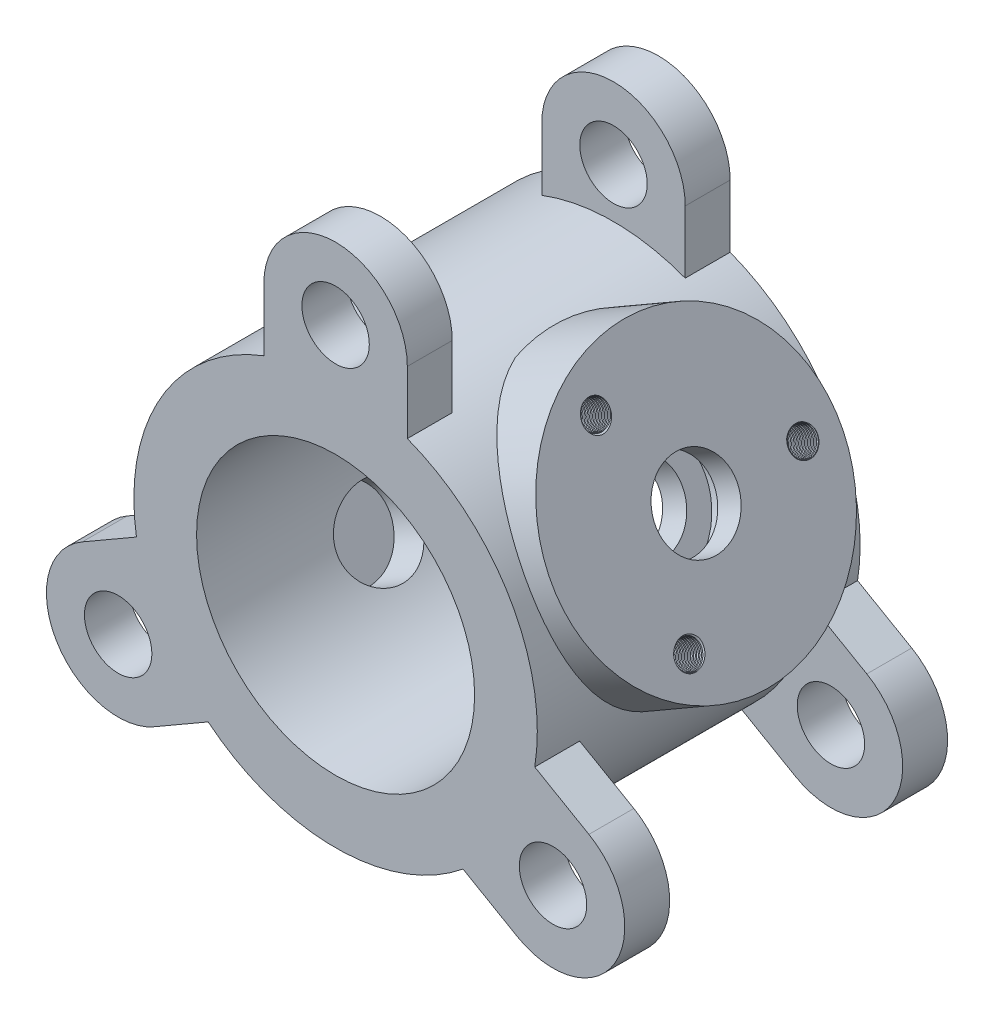
SolidWorks part; units mm, degrees
note: The reader was unsure of these and kept them because the rebuilt part matched: shared geometry of "Sketch1<5>".
ref_plane "Front Plane" through (0, 0, 0) normal (0, 0, 1) x (1, 0, 0)
ref_plane "Top Plane" through (0, 0, 0) normal (0, 1, 0) x (1, 0, 0)
ref_plane "Right Plane" through (0, 0, 0) normal (1, 0, 0) x (0, 0, -1)
sketch "Sketch1" plane through (0, 0, 0) normal (0, 0, 1) x (1, 0, 0)
  line L0 (44.8448, -11.2265) -> (35.2561, -5.6904)
  line L1 (-12.7, 44.45) -> (-12.7, 33.3779)
  line L2 (22.5561, -27.6875) -> (32.1448, -33.2235)
  line L3 (12.7, 33.3779) -> (12.7, 44.45)
  line L4 (-32.1448, -33.2235) -> (-22.5561, -27.6875)
  line L5 (-35.2561, -5.6904) -> (-44.8448, -11.2265)
  circle A0 centre (0, 0) radius 35.7124
  circle A1 centre (0, 0) radius 24.6126
  arc A2 (-12.7, 44.45) -> (12.7, 44.45) centre (0, 44.45) cw
  circle A3 centre (0, 44.45) radius 5.969
  arc A4 (44.8448, -11.2265) -> (32.1448, -33.2235) centre (38.4948, -22.225) cw
  circle A5 centre (38.4948, -22.225) radius 5.969
  arc A6 (-32.1448, -33.2235) -> (-44.8448, -11.2265) centre (-38.4948, -22.225) cw
  circle A7 centre (-38.4948, -22.225) radius 5.969
  point P24 (0, 0)
  dimension "D1" = 3
extrude "Boss-Extrude1" add sketch "Sketch1" along normal blind 28.575 contours A0 A1
extrude "Boss-Extrude3" add sketch "Sketch1<5>" along normal blind 7.9502 contours A2 L1 A0 L3 A3 | A4 L0 A0 L2 A5 | A6 L4 A0 L5 A7
sketch "Sketch1<5>" plane through (0, 0, 0) normal (0, 0, 1) x (1, 0, 0) same geometry as "Sketch1"
mirror "Mirror1" about plane through (0, 0, 28.575) normal (0, 0, 1) of "Boss-Extrude3", "Boss-Extrude1"
ref_plane "Plane1" through (30.9278, 17.8562, 0) normal (0.866, 0.5, 0) x (0, 0, -1)
sketch "Sketch3" plane through (30.9278, 17.8562, 0) normal (0.866, 0.5, 0) x (0, 0, -1)
  circle A0 centre (-28.3923, 0) radius 25.4
  point P4 (-28.3923, 19.05)
  point P5 (-44.6619, -9.525)
  point P6 (-12.2192, -9.525)
ref_plane "Plane2" through (-30.9278, -17.8562, 0) normal (-0.866, -0.5, 0) x (0, 0, 1)
extrude "Boss-Extrude5" add sketch "Sketch3" against normal blind 9.525 and the other way blind 4.7752
sketch "Sketch6" plane through (-30.9278, -17.8562, 0) normal (-0.866, -0.5, 0) x (0, 0, 1)
  line L0 (28.356, 52.8903) -> (28.356, 0) construction
  circle A0 centre (28.356, 0) radius 7.1374
  dimension "D1" = 14.2748
extrude "Boss-Extrude6" add sketch "Sketch6" along normal blind 6.35 separate body
ref_plane "Plane3" through (35.5032, 20.4978, 0) normal (0.866, 0.5, 0) x (0, 0, -1)
sketch "Sketch10" plane through (35.5032, 20.4978, 0) normal (0.866, 0.5, 0) x (0, 0, -1)
  circle A0 centre (-28.3923, 0) radius 7.1374
  dimension "D1" = 14.2748
extrude "Cut-Extrude3" cut sketch "Sketch10" against normal blind 71.4502 contours A0
hole_wizard "CBORE for #10 Binding Head Machine Screw1" positions "Sketch25" profile "Sketch26" counterbore size "#10" standard "ANSI Inch"
sketch "Sketch25" plane through (30.9278, 17.8562, 0) normal (0.866, 0.5, 0) x (0, 0, -1)
  point P0 (-28.3923, 0)
sketch "Sketch26" plane through (30.9278, 17.8562, 28.3923) normal (0, 0, 1) x (-0.5, 0.866, 0)
  line L0 (0, 0) -> (0, 53.6038)
  line L1 (0, 53.6038) -> (2.5527, 52.07)
  line L2 (2.5527, 52.07) -> (2.5527, 6.35)
  line L3 (2.5527, 6.35) -> (11.1125, 6.35)
  line L4 (11.1125, 6.35) -> (11.1125, 0)
  line L5 (11.1125, 0) -> (0, 0)
  line L10 (0, 53.6038) -> (-2.5527, 52.07) construction
  line L11 (0, -6.35) -> (0, 107.95) construction
  dimension "Hole Dia." = 5.1054
  dimension "Hole Depth" = 52.07
  dimension "C'Bore Dia." = 22.225
  dimension "C'Bore Depth" = 6.35
  dimension "Drill Angle" = 118
sketch "Sketch32" plane through (35.5032, 20.4978, 0) normal (0.866, 0.5, 0) x (0, 0, -1)
  circle A1 centre (-9.3423, 0) radius 2.413
  dimension "D2" = 4.826
extrude "Cut-Extrude4" cut sketch "Sketch32" against normal blind 9.525
sketch "Sketch35" plane through (35.5032, 20.4978, 0) normal (0.866, 0.5, 0) x (0, 0, -1)
  circle A0 centre (-9.3423, 0) radius 2.4722
curve "Helix/Spiral2" pitch 0.6233 height 9.5049 turns 15.25
ref_plane "Plane5" through (27.2717, 15.7453, 6.8701) normal (0.4649, -0.8854, 0) x (-0.8854, -0.4649, 0)
sketch "Sketch36" plane through (27.2717, 15.7453, 6.8701) normal (0.4649, -0.8854, 0) x (-0.8854, -0.4649, 0)
  line L1 (-0.0148, 0.2309) -> (-0.2105, -0.1082)
  line L2 (-0.2105, -0.1082) -> (0.181, -0.1082)
  line L3 (0.181, -0.1082) -> (-0.0148, 0.2309)
  circle A0 centre (-0.0148, 0.0048) radius 0.113 construction
sweep "Cut-Sweep2" cut profiles "Sketch36" path "Helix/Spiral2"
pattern_circular "CirPattern1" count 3 over 360 about axis through (35.0633, 20.2438, 28.3923) along (0.866, 0.5, 0) of "Cut-Sweep2", "Cut-Extrude4"
